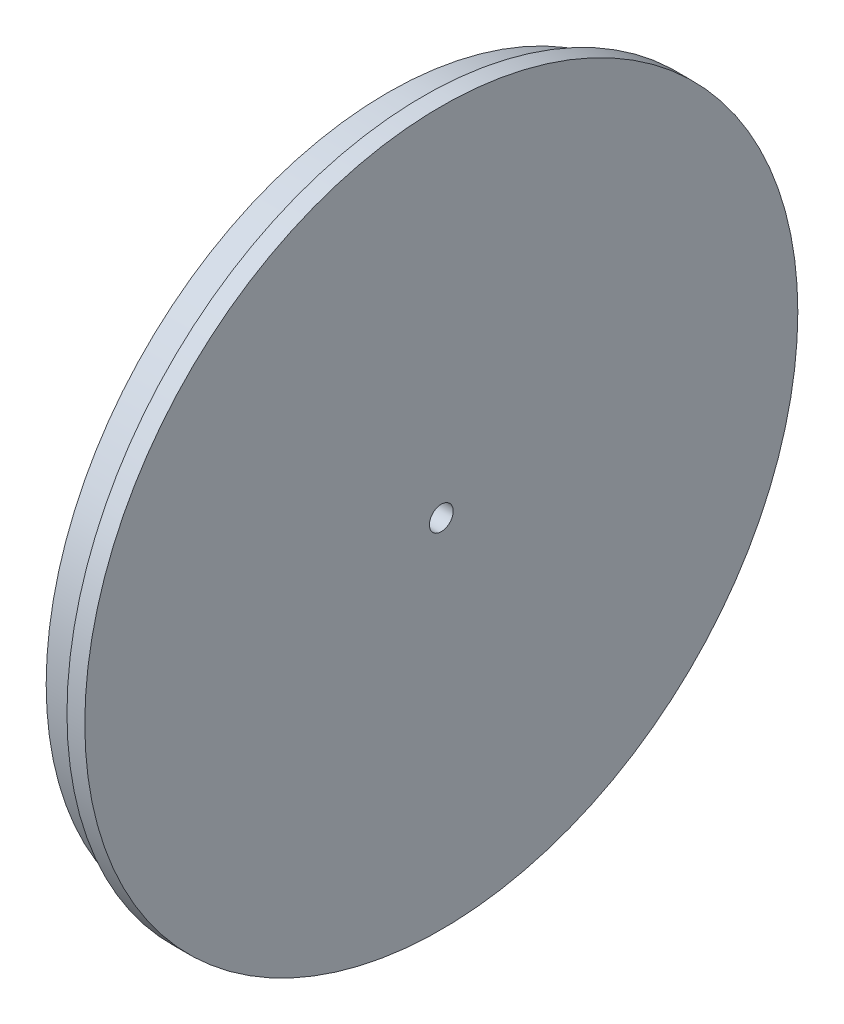
SolidWorks part; units mm, degrees
ref_plane "Plane1" through (0, 0, 0) normal (0, 0, 1) x (1, 0, 0)
ref_plane "Plane2" through (0, 0, 0) normal (0, 1, 0) x (1, 0, 0)
ref_plane "Plane3" through (0, 0, 0) normal (1, 0, 0) x (0, 0, -1)
sketch "HoldingSke" plane through (0, 0, 0) normal (0, 1, 0) x (1, 0, 0)
  line L0 (0, 0) -> (0.3214, -0.383)
  line L1 (-15, 0) -> (100, 0) construction
  line L2 (0, 0) -> (-2.1039, 2.3779)
  line L3 (0, 0) -> (-11.863, 4.5341)
  line L4 (0, 0) -> (5.5511, 6.6156)
  line L5 (0, 0) -> (-23.7986, -8.8762)
  line L6 (0, 0) -> (-10.5278, -7.1032)
  line L7 (-2.1039, 2.3779) -> (3.3635, 27.1825)
  line L8 (-76.2, 4.3779) -> (-54.61, 4.3779)
  line L9 (-71.009, 38.7566) -> (-53.1078, 45.2721)
  line L10 (-76.2, 71.12) -> (104.1128, 71.12)
  line L11 (0, 0) -> (-6, 0)
  line L12 (-76.2, 101.6) -> (-76.133, 101.6)
  line L13 (24.9733, 27.94) -> (52.9518, 28.4284)
  line L14 (24.9733, 27.94) -> (24.9743, 27.94)
  line L15 (24.9733, 27.94) -> (100.4006, 29.5858)
  circle A0 centre (0, 0) radius 57.5
  circle A1 centre (0, 0) radius 12.7
  circle A2 centre (0, 0) radius 12.7
  dimension "MHD" = 25.4
  dimension "Hub_dia" = 25.4
  dimension "Diameter" = 115
  dimension "Num_teeth" = 50
  dimension "Pitch_radius" = 180.3128
  dimension "Pitch" = 0.5
  dimension "Width" = 6
  dimension "Overall_len" = 25.4
  dimension "Show_teeth" = 50
  dimension "Thickness" = 12.7
  dimension "OAL" = 25.4001
  dimension "T_dim" = 21.59
  dimension "Ap" = 20
  dimension "H" = 19.05
  dimension "Backlash" = 0.067
  dimension "Addendum_fac" = 1
  dimension "Dedendum_fac" = 1.25
  dimension "Clearance_fac" = 0.25
  dimension "Dedendum_add" = 0.001
  dimension "Module" = 2
sketch "BasProSke" plane through (0, 0, 0) normal (0, 1, 0) x (1, 0, 0)
  line L0 (-10, 0) -> (60, 0) construction
  line L1 (0, 48) -> (0, 57.5)
  line L2 (0, 48) -> (6, 48)
  line L3 (6, 48) -> (6, 57.5)
  line L4 (6, 57.5) -> (0, 57.5)
  dimension "Diameter" = 115
  dimension "Thickness" = 6
  dimension "Inside_diameter" = 96
revolve "Base-Revolve" add sketch "BasProSke" angle 360 about L0
sketch "TooCutSke" plane through (0, 0, 0) normal (1, 0, 0) x (0, 0, -1)
  line L3 (1.738, 49.9698) -> (1.738, 53.6633) construction
  line L4 (0, 0) -> (0, 59.563) construction
  line L5 (0, 0) -> (-4.2903, 68.1927) construction
  line L6 (-21.6015, 41.0107) -> (35.113, 44.5789) construction
  circle A0 centre (0, 0) radius 50 construction
  circle A1 centre (0, 0) radius 52.501 construction
  circle A2 centre (0, 0) radius 42.2862 construction
  circle A3 centre (0, 0) radius 47.9746 construction
  arc A4 (2.4267, 47.9132) -> (0.6033, 52.4975) centre (-21.6015, 41.0107) ccw
  arc A5 (2.4267, 47.9132) -> (-2.4267, 47.9132) centre (0, 0) ccw
  arc A6 (0.6033, 52.4975) -> (-0.6033, 52.4975) centre (0, 0) ccw
  arc A7 (-0.6033, 52.4975) -> (-2.4267, 47.9132) centre (21.6015, 41.0107) ccw
  dimension "Pitch_dia" = 100
  dimension "Base_dia" = 84.5723
  dimension "Root_dia" = 105.002
  dimension "Overcut_dia" = 95.9492
  dimension "Flank_rad" = 25
  dimension "Half_ang" = 3.6
  dimension "Half_CT" = 1.738
extrude "ToothCut" cut sketch "TooCutSke" along normal through all
fillet "Breaks" [suppressed] radius 0.2
fillet "RootFillets" [suppressed] radius 0.501
pattern_circular "TeethCuts" count 50 over 360 about axis through (-10, 0, 0) along (1, 0, 0) of "RootFillets", "Breaks", "ToothCut"
sketch "Esquisse1" plane through (6, 0, 0) normal (1, 0, 0) x (0, 0, -1)
  circle A0 centre (0, 0) radius 60
  circle A1 centre (0, 0) radius 2
  dimension "D1" = 120
  dimension "D2" = 4
extrude "Boss.-Extru.1" add sketch "Esquisse1" along normal blind 3
sketch "Esquisse2" plane through (6, 0, 0) normal (-1, 0, 0) x (0, 0, 1)
  circle A0 centre (0, 0) radius 10
  circle A1 centre (0, 0) radius 2
  dimension "D1" = 20
extrude "Boss.-Extru.2" add sketch "Esquisse2" along normal blind 10
sketch "Esquisse3" plane through (-4, 0, 0) normal (-1, 0, 0) x (0, 0, 1)
  line L0 (0, 10) -> (0, -10) construction
  line L1 (-2.75, 6) -> (2.75, 6)
  line L2 (-2.75, 6) -> (-2.75, 4)
  line L3 (-2.75, 4) -> (2.75, 4)
  line L4 (2.75, 6) -> (2.75, 4)
  line L5 (-2.75, 6) -> (2.75, 4) construction
  line L6 (-2.75, 4) -> (2.75, 6) construction
  line L7 (-10, 0) -> (10, 0) construction
  circle A0 centre (0, 0) radius 10 construction
  circle A1 centre (0, 0) radius 10 construction
  point P0 (0, 5)
  dimension "D1" = 5.5
  dimension "D2" = 2
  dimension "D3" = 5
extrude "Enlèv. mat.-Extru.1" cut sketch "Esquisse3" against normal blind 7
sketch "Esquisse4" plane through (0, 4, 0) normal (0, 1, 0) x (1, 0, 0)
  circle A0 centre (0, 0) radius 1.5
  dimension "D1" = 3
extrude "Enlèv. mat.-Extru.2" cut sketch "Esquisse4" against normal up to next and the other way up to next
equation "' \"Module@HoldingSke\" = 6.35"
equation "' \"Num_teeth@HoldingSke\" = 24"
equation "' \"Ap@HoldingSke\" =  14.5"
equation "' \"Width@HoldingSke\" = 12"
equation "' \"Diameter@HoldingSke\" = 8 * 25.4"
equation "' \"Show_teeth@HoldingSke\" = 100"
equation "' \"Backlash@HoldingSke\" = 0.009 * 25.4"
equation "' \"Addendum_fac@HoldingSke\" = 1.0"
equation "' \"Dedendum_fac@HoldingSke\" = 1.25"
equation "' \"Dedendum_add@HoldingSke\" = 0.00005 * 25.4"
equation "' \"Clearance_fac@HoldingSke\" = 0.25"
equation "\"Pitch@HoldingSke\" = 1 / \"Module@HoldingSke\" "
equation "\"Overcut_dia@TooCutSke\" = (\"Num_teeth@HoldingSke\" - 2 * \"Addendum_fac@HoldingSke\") / \"Pitch@HoldingSke\" - 0.002 * 25.4"
equation "\"Pitch_dia@TooCutSke\" = \"Num_teeth@HoldingSke\" / \"Pitch@HoldingSke\""
equation "\"Base_dia@TooCutSke\" = \"Num_teeth@HoldingSke\" / \"Pitch@HoldingSke\" * cos((\"Ap@HoldingSke\"  * 3.14159265 / 180)) * 0.90"
equation "\"Root_dia@TooCutSke\" = \"Num_teeth@HoldingSke\"  / \"Pitch@HoldingSke\" + 2 *  \"Dedendum_fac@HoldingSke\"/ \"Pitch@HoldingSke\" + \"Dedendum_add@HoldingSke\" * 2"
equation "\"Half_ang@TooCutSke\" = 180 / \"Num_teeth@HoldingSke\""
equation "\"Half_CT@TooCutSke\" = \"Num_teeth@HoldingSke\" / \"Pitch@HoldingSke\" * sin((3.14159265 / 2 / \"Num_teeth@HoldingSke\")) / 2 + 10 * \"Backlash@HoldingSke\" / 4"
equation "\"Flank_rad@TooCutSke\" = \"Num_teeth@HoldingSke\" / \"Pitch@HoldingSke\" / 4"
equation "\"Radius@RootFillets\"= \"Clearance_fac@HoldingSke\" / \"Pitch@HoldingSke\" + \"Dedendum_add@HoldingSke\""
equation "\"Break_rad@Breaks\" = 0.02 / \"Pitch@HoldingSke\" * 5"
equation "\"Num_teeth@TeethCuts\" = int( \"Show_teeth@HoldingSke\" ) + 1"
equation "\"Num_teeth@TeethCuts\" = ((sgn( \"Num_teeth@TeethCuts\" - \"Num_teeth@HoldingSke\" )-1)*( \"Num_teeth@TeethCuts\" - \"Num_teeth@HoldingSke\" ))/-2+ \"Num_teeth@HoldingSke\""
equation "\"Num_teeth@TeethCuts\" = ((sgn( \"Num_teeth@TeethCuts\" - 2.0)+1)*( \"Num_teeth@TeethCuts\" - 2.0))/2 +2.0"
equation "\"Angle@TeethCuts\" = 360.0 / \"Num_teeth@HoldingSke\""
equation "\"Diameter@BasProSke\" = \"Num_teeth@HoldingSke\"  / \"Pitch@HoldingSke\" + 2 *  \"Dedendum_fac@HoldingSke\"/ \"Pitch@HoldingSke\" + \"Dedendum_add@HoldingSke\" * 2 + 0.002 * 25.4"
equation "\"Diameter@BasProSke\" = ((sgn( \"Diameter@BasProSke\"  - \"Diameter@HoldingSke\" )+1)*( \"Diameter@BasProSke\"  - \"Diameter@HoldingSke\" ))/2 + \"Diameter@HoldingSke\""
equation "\"Inside_diameter@BasProSke\" =  (\"Num_teeth@HoldingSke\" - 2 * \"Addendum_fac@HoldingSke\") / \"Pitch@HoldingSke\" "
equation "\"Thickness@BasProSke\"  = \"Width@HoldingSke\""
